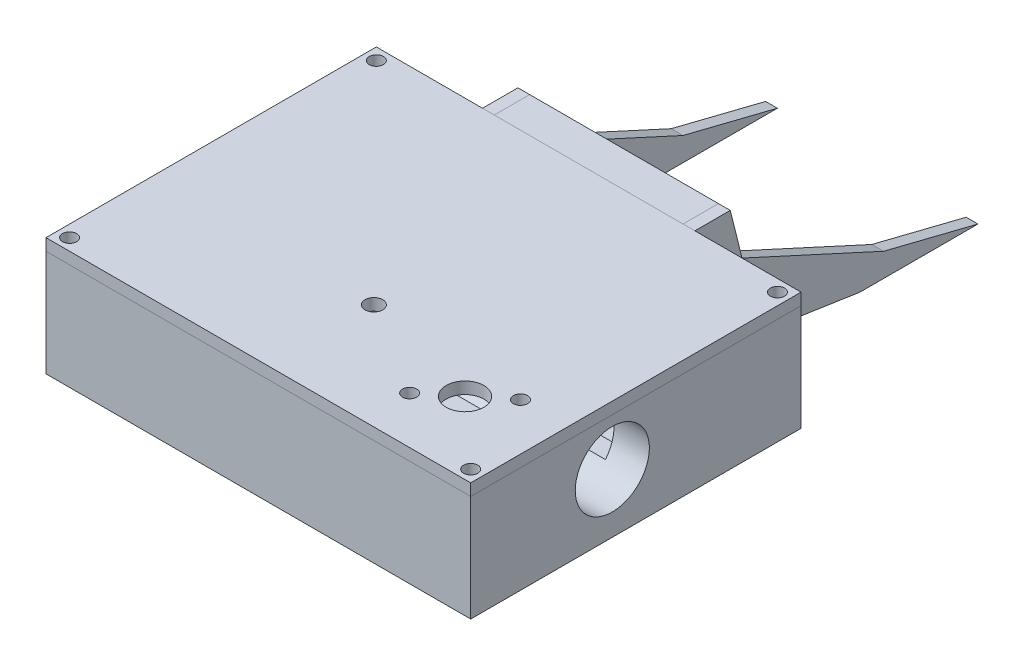
SolidWorks part; units mm, degrees
material "PLA/ABS"
ref_plane "Front Plane" through (0, 0, 0) normal (0, 0, 1) x (1, 0, 0)
ref_plane "Top Plane" through (0, 0, 0) normal (0, 1, 0) x (1, 0, 0)
ref_plane "Right Plane" through (0, 0, 0) normal (1, 0, 0) x (0, 0, -1)
other "Center of Mass"
other "Bounding Box"
ref_plane "Default Plane" through (-8.9266, -12.7485, 0) normal (-0.1736, 0.9848, 0) x (0.9848, 0.1736, 0)
sketch "Sketch1" plane through (0, 0, 0) normal (0, 1, 0) x (1, 0, 0)
  line L0 (0, 0) -> (0, -50.8) construction
  line L1 (0, -50.8) -> (-6.35, -50.8) construction
  line L2 (-63.5, -50.8) -> (-57.15, -50.8) construction
  line L3 (-57.15, -60.7695) -> (-6.35, -60.7695)
  line L4 (-57.15, -60.7695) -> (-57.15, -40.8305)
  line L5 (-57.15, -40.8305) -> (-6.35, -40.8305)
  line L6 (-6.35, -60.7695) -> (-6.35, -40.8305)
  line L7 (-57.15, -60.7695) -> (-6.35, -40.8305) construction
  line L8 (-57.15, -40.8305) -> (-6.35, -60.7695) construction
  line L9 (-73.66, -71.4375) -> (-63.5, -71.4375)
  line L10 (-73.66, -71.4375) -> (-73.66, -30.1625)
  line L11 (-73.66, -30.1625) -> (-63.5, -30.1625)
  line L12 (-63.5, -71.4375) -> (-63.5, -30.1625)
  line L13 (-73.66, -71.4375) -> (-63.5, -30.1625) construction
  line L14 (-73.66, -30.1625) -> (-63.5, -71.4375) construction
  line L15 (57.15, -40.8305) -> (6.35, -40.8305)
  line L16 (-47.625, -82.55) -> (9.525, -82.55)
  line L17 (-47.625, -82.55) -> (-47.625, -66.04)
  line L18 (-47.625, -66.04) -> (9.525, -66.04)
  line L19 (9.525, -82.55) -> (9.525, -66.04)
  line L20 (-47.625, -82.55) -> (9.525, -66.04) construction
  line L21 (-47.625, -66.04) -> (9.525, -82.55) construction
  line L22 (6.35, -60.7695) -> (6.35, -40.8305)
  line L23 (57.15, -60.7695) -> (6.35, -60.7695)
  line L24 (57.15, -60.7695) -> (57.15, -40.8305)
  line L25 (73.66, -30.1625) -> (63.5, -30.1625)
  line L26 (63.5, -71.4375) -> (63.5, -30.1625)
  line L27 (73.66, -71.4375) -> (63.5, -71.4375)
  line L28 (73.66, -71.4375) -> (73.66, -30.1625)
  line L30 (47.625, -82.55) -> (4.445, -82.55)
  line L31 (47.625, -82.55) -> (47.625, -62.4078)
  line L32 (47.625, -62.4078) -> (4.445, -62.4078)
  line L33 (4.445, -82.55) -> (4.445, -62.4078)
  line L34 (47.625, -82.55) -> (4.445, -62.4078) construction
  line L35 (47.625, -62.4078) -> (4.445, -82.55) construction
  line L36 (-57.15, -88.9) -> (57.15, -88.9)
  line L37 (-57.15, -88.9) -> (-57.15, 0)
  line L38 (-57.15, 0) -> (57.15, 0)
  line L39 (57.15, -88.9) -> (57.15, 0)
  line L40 (-57.15, -88.9) -> (57.15, 0) construction
  line L41 (-57.15, 0) -> (57.15, -88.9) construction
  point P1 (0, -36.5533)
  point P3 (-19.05, -74.295)
  point P6 (-31.75, -50.8)
  point P12 (-68.58, -50.8)
  point P22 (0, 0)
  point P23 (0, -44.45)
  point P36 (0, 6.35)
  point P37 (0, 0)
  point P38 (26.035, -72.4789)
  dimension "D2" = 50.8
  dimension "D3" = 19.939
  dimension "D4" = 41.275
  dimension "D5" = 10.16
  dimension "D6" = 57.15
  dimension "D7" = 16.51
  dimension "D8" = 43.18
  dimension "D9" = 20.1422
  dimension "D10" = 6.35
  dimension "D11" = 114.3
  dimension "D12" = 38.1
  dimension "D13" = 6.35
  dimension "D14" = 9.525
  dimension "D15" = 6.35
  dimension "D16" = 9.525
  dimension "D17" = 88.9
  dimension "D18" = 6.35
sketch "Sketch2" plane through (0, 0, 0) normal (1, 0, 0) x (0, 0, -1)
  line L1 (-88.9, 12.7) -> (0, 12.7)
  line L2 (-88.9, 12.7) -> (-88.9, -12.7)
  line L3 (-88.9, -12.7) -> (0, -12.7)
  line L4 (0, 12.7) -> (0, -12.7)
  line L5 (-88.9, 12.7) -> (0, -12.7) construction
  line L6 (-88.9, -12.7) -> (0, 12.7) construction
  line L7 (-88.9, 12.7) -> (12.7, 12.7)
  line L8 (-88.9, 12.7) -> (-88.9, 15.875)
  line L9 (-88.9, 15.875) -> (12.7, 15.875)
  line L10 (12.7, 12.7) -> (12.7, 15.875)
  line L11 (-88.9, 12.7) -> (12.7, 15.875) construction
  line L12 (-88.9, 15.875) -> (12.7, 12.7) construction
  line L13 (-88.9, -12.7) -> (0, -12.7)
  line L14 (-88.9, -12.7) -> (-88.9, -15.875)
  line L15 (-88.9, -15.875) -> (0, -15.875)
  line L16 (0, -12.7) -> (0, -15.875)
  line L17 (-88.9, -12.7) -> (0, -15.875) construction
  line L18 (-88.9, -15.875) -> (0, -12.7) construction
  circle A0 centre (-50.8, 0) radius 20.6375
  point P4 (-71.4375, 0)
  point P5 (-44.45, 0)
  point P15 (-38.1, 14.2875)
  point P19 (-44.45, -14.2875)
  point P24 (22.811, -9.9402)
  dimension "D1" = 25.4
  dimension "D2" = 3.175
  dimension "D3" = 12.7
sketch "Sketch3" plane through (0, 0, 0) normal (0, 1, 0) x (1, 0, 0)
  line L1 (-57.15, -88.9) -> (57.15, -88.9)
  line L2 (-57.15, -88.9) -> (-57.15, 0)
  line L3 (-57.15, 0) -> (57.15, 0)
  line L4 (57.15, -88.9) -> (57.15, 0)
  line L5 (-57.15, -88.9) -> (57.15, 0) construction
  line L6 (-57.15, 0) -> (57.15, -88.9) construction
  line L7 (-47.625, -6.35) -> (47.625, -6.35)
  line L8 (-47.625, -6.35) -> (-47.625, -82.55)
  line L9 (-47.625, -82.55) -> (47.625, -82.55)
  line L10 (47.625, -6.35) -> (47.625, -82.55)
  line L11 (-47.625, -6.35) -> (47.625, -82.55) construction
  line L12 (-47.625, -82.55) -> (47.625, -6.35) construction
  point P0 (0, -44.45)
  point P7 (0, -44.45)
extrude "Boss-Extrude1" add sketch "Sketch3" along normal up to vertex (12.7 mm away) and the other way up to vertex (12.7 mm away) up to point (0, 12.7, 88.9) other way up to point (0, -12.7, 88.9)
sketch "Sketch4" plane through (0, -12.7, 0) normal (0, -1, 0) x (1, 0, 0)
  line L1 (-57.15, 88.9) -> (57.15, 88.9)
  line L2 (-57.15, 88.9) -> (-57.15, 0)
  line L3 (-57.15, 0) -> (57.15, 0)
  line L4 (57.15, 88.9) -> (57.15, 0)
  line L5 (-57.15, 88.9) -> (57.15, 0) construction
  line L6 (-57.15, 0) -> (57.15, 88.9) construction
  point P0 (0, 44.45)
extrude "Boss-Extrude2" add sketch "Sketch4" along normal up to vertex (3.175 mm away) up to point (0, -15.875, 88.9)
sketch "Sketch5" plane through (0, 12.7, 0) normal (0, 1, 0) x (1, 0, 0)
  line L1 (-57.15, 0) -> (-57.15, -88.9)
  line L2 (-57.15, -88.9) -> (57.15, -88.9)
  line L3 (57.15, -88.9) -> (57.15, 0)
  line L5 (-57.15, 0) -> (57.15, 0)
extrude "Boss-Extrude3" add sketch "Sketch5" along normal up to vertex (3.175 mm away) separate body up to point (0, 15.875, 88.9)
sketch "Sketch7" plane through (0, -12.7, 0) normal (0, 1, 0) x (1, 0, 0)
  line L0 (-6.35, -60.7695) -> (-6.35, -40.8305) construction
  line L1 (-47.625, -38.1) -> (-6.35, -38.1)
  line L2 (-47.625, -38.1) -> (-47.625, -63.5)
  line L3 (-47.625, -63.5) -> (-6.35, -63.5)
  line L4 (-6.35, -38.1) -> (-6.35, -63.5)
  line L5 (-47.625, -38.1) -> (-6.35, -63.5) construction
  line L6 (-47.625, -63.5) -> (-6.35, -38.1) construction
  line L7 (47.625, -38.1) -> (6.35, -38.1)
  line L8 (47.625, -38.1) -> (47.625, -63.5)
  line L9 (47.625, -63.5) -> (6.35, -63.5)
  line L10 (6.35, -38.1) -> (6.35, -63.5)
  line L11 (47.625, -38.1) -> (6.35, -63.5) construction
  line L12 (47.625, -63.5) -> (6.35, -38.1) construction
  line L13 (6.35, -60.7695) -> (6.35, -40.8305) construction
  line L14 (0, -50.8) -> (-6.35, -50.8) construction
  line L15 (47.625, -82.55) -> (47.625, -6.35) construction
  line L16 (-47.625, -6.35) -> (-47.625, -82.55) construction
  point P4 (-26.9875, -50.8)
  point P10 (26.9875, -50.8)
  point P12 (47.8999, -16.1156)
  point P13 (-6.35, -47.3844)
  point P18 (-6.35, -45.142)
  point P21 (50.8, -45.6404)
  point P24 (-50.8, -19.05)
  dimension "D1" = 25.4
extrude "Boss-Extrude4" add sketch "Sketch7" along normal blind 6.35
sketch "Sketch6" plane through (-57.15, 0, 0) normal (-1, 0, 0) x (0, 0, 1)
  circle A0 centre (50.8, 0) radius 9.9695
extrude "Cut-Extrude1" cut sketch "Sketch6" against normal through all
ref_plane "Plane1" through (0, 0, 0) normal (1, 0, 0) x (0, 0, -1)
sketch "Sketch13" plane through (0, -12.7, 0) normal (0, 1, 0) x (1, 0, 0)
  line L0 (-47.625, -63.5) -> (-6.35, -63.5) construction
  line L1 (-6.35, -38.1) -> (-32.385, -38.1)
  line L2 (-6.35, -38.1) -> (-6.35, -63.5)
  line L3 (-6.35, -63.5) -> (-32.385, -63.5)
  line L4 (-32.385, -38.1) -> (-32.385, -63.5)
  line L5 (-6.35, -38.1) -> (-32.385, -63.5) construction
  line L6 (-6.35, -63.5) -> (-32.385, -38.1) construction
  line L7 (-47.625, -38.1) -> (-47.625, -43.1144) construction
  line L9 (0, -55) -> (0, 55) construction
  line L10 (32.385, -38.1) -> (32.385, -63.5)
  line L11 (6.35, -63.5) -> (32.385, -63.5)
  line L12 (6.35, -38.1) -> (6.35, -63.5)
  line L13 (6.35, -38.1) -> (32.385, -38.1)
  point P4 (-19.3675, -50.8)
  point P16 (-6.35, -19.05)
  dimension "D1" = 15.24
extrude "Boss-Extrude5" add sketch "Sketch13" along normal blind 4.064
sketch "Sketch19" plane through (0, 12.7, 0) normal (0, 1, 0) x (1, 0, 0)
  line L0 (-57.15, 0) -> (-57.15, -88.9) construction
  line L1 (57.15, 0) -> (-57.15, 0) construction
  line L5 (57.15, -88.9) -> (57.15, 0) construction
  line L6 (57.15, 0) -> (-57.15, 0) construction
  line L7 (-57.15, -88.9) -> (57.15, -88.9) construction
  line L8 (-47.625, -82.55) -> (47.625, -82.55) construction
  circle A0 centre (-53.975, -3.175) radius 3.175 construction
  circle A1 centre (-53.975, -3.175) radius 0.9525
  circle A2 centre (53.975, -3.175) radius 3.175 construction
  circle A3 centre (53.975, -3.175) radius 0.9525
  circle A4 centre (-53.975, -85.725) radius 3.175 construction
  circle A5 centre (-53.975, -85.725) radius 0.9525
  circle A6 centre (53.975, -85.725) radius 3.175 construction
  circle A7 centre (53.975, -85.725) radius 0.9525
  dimension "D1" = 1.905
  dimension "D2" = 6.35
extrude "Cut-Extrude4" cut sketch "Sketch19" against normal blind 25.4
sketch "Sketch20" plane through (0, 15.875, 0) normal (0, 1, 0) x (1, 0, 0)
  circle A0 centre (-53.975, -3.175) radius 1.905
  circle A1 centre (-53.975, -85.725) radius 1.905
  circle A2 centre (53.975, -85.725) radius 1.905
  circle A3 centre (53.975, -3.175) radius 1.905
  dimension "D1" = 3.81
  dimension "D2" = 3.81
  dimension "D3" = 3.81
  dimension "D4" = 3.81
extrude "Cut-Extrude7" cut sketch "Sketch20" against normal up to surface (3.175 mm away) up to face at (0, 12.7, 44.45)
sketch "Sketch23" plane through (0, 15.875, 0) normal (0, 1, 0) x (1, 0, 0)
  line L0 (-57.15, -88.9) -> (57.15, -88.9) construction
  line L1 (44.45, -62.8085) -> (28.015, -62.8085) construction
  line L2 (44.45, -62.8085) -> (44.45, -76.2) construction
  line L3 (44.45, -76.2) -> (28.015, -76.2) construction
  line L4 (28.015, -62.8085) -> (28.015, -76.2) construction
  line L5 (44.45, -62.8085) -> (28.015, -76.2) construction
  line L6 (44.45, -76.2) -> (28.015, -62.8085) construction
  line L7 (57.15, -88.9) -> (57.15, 0) construction
  circle A0 centre (36.2325, -69.5043) radius 5.08
  circle A1 centre (44.45, -62.8085) radius 1.905
  circle A2 centre (28.015, -76.2) radius 1.905
  circle A4 centre (2.615, -60.4273) radius 2.3812
  point P0 (36.2325, -69.5043)
  dimension "D1" = 10.16
  dimension "D2" = 3.81
  dimension "D3" = 10.6
  dimension "D4" = 12.7
  dimension "D7" = 4.7625
  dimension "D8" = 25.4
  dimension "D5" = 12.7
  dimension "D6" = 13.3915
extrude "Cut-Extrude8" cut sketch "Sketch23" against normal up to surface (3.175 mm away) up to face at (53.975, 12.7, 5.08)
delete or keep bodies "Body-Delete/Keep 1" [suppressed] type delete bodies bodies 114
sketch "Sketch25" plane through (0, 0, 0) normal (1, 0, 0) x (0, 0, -1)
  line L0 (0, -15.875) -> (0, 15.875)
  line L1 (0, 15.875) -> (9.525, 15.875)
  line L2 (9.525, 15.875) -> (12.7, 3.175)
  line L3 (12.7, 3.175) -> (12.7, -15.875)
  line L4 (12.7, -15.875) -> (0, -15.875)
  dimension "D1" = 12.7
  dimension "D2" = 9.525
  dimension "D3" = 19.05
extrude "Boss-Extrude6" add sketch "Sketch25" along normal mid plane 50.8
sketch "Sketch26" plane through (25.4, 0, 0) normal (1, 0, 0) x (0, 0, -1)
  line L0 (-91.2367, -20.6375) -> (2.1353, -20.6375) construction
  line L1 (0, 15.875) -> (9.525, 15.875)
  line L2 (9.525, 15.875) -> (12.7, 3.175)
  line L3 (12.7, 3.175) -> (50.8, -14.2875)
  line L4 (76.2, -20.6375) -> (44.45, -20.6375)
  line L5 (44.45, -20.6375) -> (12.7, -15.875)
  line L6 (12.7, -15.875) -> (0, -15.875)
  line L7 (0, -15.875) -> (0, 15.875)
  line L8 (12.7, -15.875) -> (12.7, 3.175) construction
  line L10 (76.2, -20.6375) -> (50.8, -14.2875)
  circle A0 centre (-50.8, 0) radius 20.6375 construction
  point P15 (50.3199, -14.9129)
  point P20 (53.3859, -20.6375)
  dimension "D1" = 63.5
  dimension "D2" = 31.75
  dimension "D3" = 6.35
  dimension "D4" = 25.4
extrude "Boss-Extrude7" add sketch "Sketch26" along normal blind 3.175 separate body
sketch "Sketch27" plane through (25.4, 0, 0) normal (1, 0, 0) x (0, 0, -1)
  line L0 (0, -9.525) -> (6.35, -9.525) construction
  line L1 (0, 12.7) -> (0, -12.7) construction
  line L2 (6.35, -9.525) -> (12.7, -9.525) construction
  line L4 (12.7, -15.875) -> (12.7, 3.175) construction
  line L5 (6.35, -9.525) -> (6.35, 3.175) construction
  line L6 (0, -15.875) -> (12.7, -15.875) construction
  circle A0 centre (6.35, -9.525) radius 4.7625
  circle A1 centre (6.35, 3.175) radius 4.7625
  dimension "D1" = 9.525
  dimension "D2" = 6.35
  dimension "D3" = 12.7
extrude "Cut-Extrude9" cut sketch "Sketch27" against normal through all and the other way through all
sketch "Sketch28" plane through (25.4, 0, 0) normal (-1, 0, 0) x (0, 0, 1)
  circle A0 centre (-6.35, 3.175) radius 2.5527
  circle A1 centre (-6.35, -9.525) radius 2.5527
  dimension "D1" = 5.1054
extrude "Cut-Extrude10" cut sketch "Sketch28" against normal through all
mirror "Mirror1" about plane through (0, 0, 0) normal (1, 0, 0) of bodies 123 120
